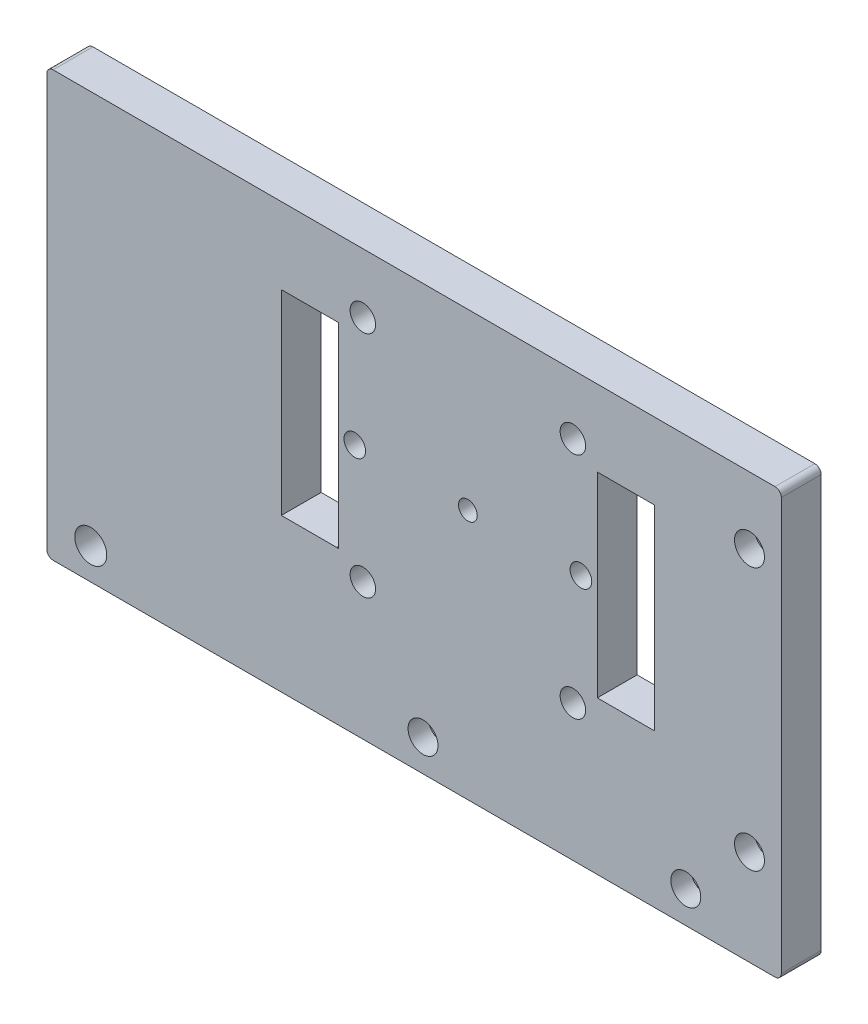
SolidWorks part; units mm, degrees
ref_plane "Front Plane" through (0, 0, 0) normal (0, 0, 1) x (1, 0, 0)
ref_plane "Top Plane" through (0, 0, 0) normal (0, 1, 0) x (1, 0, 0)
ref_plane "Right Plane" through (0, 0, 0) normal (1, 0, 0) x (0, 0, -1)
sketch "Brace Ref" plane through (0, 0, 0) normal (0, 0, 1) x (1, 0, 0)
  line B0 (-76.454, 5.6642) -> (-76.454, 10.0838)
  line B1 (-75.8588, 11.5206) -> (-73.7506, 13.6288)
  line B2 (-72.3138, 14.224) -> (-61.0148, 14.224)
  line B3 (-61.0148, 14.224) -> (-38.7641, 15.001)
  line B4 (-75.8588, 4.2274) -> (-73.7506, 2.1192)
  line B5 (-72.3138, 1.524) -> (-61.5696, 1.524)
  line B6 (-57.8366, 0) -> (-21.4114, 0)
  line B7 (-17.6784, 1.524) -> (-5.6642, 1.524)
  line B8 (-4.2274, 2.1192) -> (-2.1192, 4.2274)
  line B9 (-1.524, 5.6642) -> (-1.524, 17.6784)
  line B10 (0, 21.4114) -> (0, 57.8366)
  line B11 (-1.524, 61.5696) -> (-1.524, 72.3138)
  line B12 (-2.1192, 73.7506) -> (-4.2274, 75.8588)
  line B13 (-5.6642, 76.454) -> (-10.0838, 76.454)
  line B14 (-11.5206, 75.8588) -> (-13.6288, 73.7506)
  line B15 (-14.224, 72.3138) -> (-14.224, 61.0148)
  line B16 (-14.224, 61.0148) -> (-15.001, 38.7641)
  line B17 (-76.454, 0) -> (-76.454, 76.454) construction
  line B18 (-76.454, 0) -> (0, 0) construction
  line B19 (0, 0) -> (0, 76.454) construction
  line B20 (-76.454, 76.454) -> (0, 76.454) construction
  arc B21 (-76.454, 10.0838) -> (-75.8588, 11.5206) centre (-74.422, 10.0838) cw
  arc B22 (-73.7506, 13.6288) -> (-72.3138, 14.224) centre (-72.3138, 12.192) cw
  arc B23 (-38.7641, 15.001) -> (-27.0035, 18.4638) centre (-39.624, 39.624) ccw
  arc B24 (-27.0035, 18.4638) -> (-25.4333, 20.7849) centre (-28.6949, 21.2997) ccw
  arc B25 (-25.4333, 20.7849) -> (-20.7849, 25.4333) centre (-19.9136, 19.9136) cw
  arc B26 (-76.454, 5.6642) -> (-75.8588, 4.2274) centre (-74.422, 5.6642) ccw
  arc B27 (-73.7506, 2.1192) -> (-72.3138, 1.524) centre (-72.3138, 3.556) ccw
  arc B28 (-61.5696, 1.524) -> (-59.2587, 0.5806) centre (-61.5696, -1.778) cw
  arc B29 (-59.2587, 0.5806) -> (-57.8366, 0) centre (-57.8366, 2.032) ccw
  arc B30 (-21.4114, 0) -> (-19.9893, 0.5806) centre (-21.4114, 2.032) ccw
  arc B31 (-19.9893, 0.5806) -> (-17.6784, 1.524) centre (-17.6784, -1.778) cw
  arc B32 (-5.6642, 1.524) -> (-4.2274, 2.1192) centre (-5.6642, 3.556) ccw
  arc B33 (-2.1192, 4.2274) -> (-1.524, 5.6642) centre (-3.556, 5.6642) ccw
  arc B34 (-1.524, 17.6784) -> (-0.5806, 19.9893) centre (1.778, 17.6784) cw
  arc B35 (-0.5806, 19.9893) -> (0, 21.4114) centre (-2.032, 21.4114) ccw
  arc B36 (0, 57.8366) -> (-0.5806, 59.2587) centre (-2.032, 57.8366) ccw
  arc B37 (-0.5806, 59.2587) -> (-1.524, 61.5696) centre (1.778, 61.5696) cw
  arc B38 (-1.524, 72.3138) -> (-2.1192, 73.7506) centre (-3.556, 72.3138) ccw
  arc B39 (-4.2274, 75.8588) -> (-5.6642, 76.454) centre (-5.6642, 74.422) ccw
  arc B40 (-10.0838, 76.454) -> (-11.5206, 75.8588) centre (-10.0838, 74.422) ccw
  arc B41 (-13.6288, 73.7506) -> (-14.224, 72.3138) centre (-12.192, 72.3138) ccw
  arc B42 (-15.001, 38.7641) -> (-18.4638, 27.0035) centre (-39.624, 39.624) cw
  arc B43 (-18.4638, 27.0035) -> (-20.7849, 25.4333) centre (-21.2997, 28.6949) cw
  circle B44 centre (-70.104, 7.874) radius 4.3561
  circle B45 centre (-19.9136, 19.9136) radius 2.3813
  circle B46 centre (-7.874, 70.104) radius 4.3561
sketch_block_instance "Block1-1"
sketch_block "Block1" parameters "D1"=31.75, "D2"=30.48, "D3"=30.48, "D4"=31.75, "D5"=19.7104, "D6"=19.7104
sketch "Sketch5" plane through (0, 0, 0) normal (0, 0, 1) x (1, 0, 0)
  line L0 (-52.794, 44.294) -> (-52.794, 42.794) construction
  line L1 (-94.544, 70.544) -> (-2.794, 70.544)
  line L2 (-94.544, 70.544) -> (-94.544, 2.794)
  line L3 (-94.544, 2.794) -> (-2.794, 2.794)
  line L4 (-2.794, 70.544) -> (-2.794, 2.794)
  line L6 (-82.794, 58.794) -> (-22.794, 58.794) construction
  line L7 (-82.794, 58.794) -> (-82.794, 26.794) construction
  line L8 (-70.828, 42.794) -> (-52.794, 42.794) construction
  line L9 (-84.544, 60.544) -> (-21.044, 60.544) construction
  line L10 (-52.794, 42.794) -> (-34.76, 42.794) construction
  line L11 (-84.544, 60.544) -> (-84.544, 25.044) construction
  line L12 (-84.544, 25.044) -> (-21.044, 25.044) construction
  line L13 (-21.044, 60.544) -> (-21.044, 25.044) construction
  line L14 (-89.544, 65.544) -> (-16.044, 65.544) construction
  line L15 (-82.794, 26.794) -> (-22.794, 26.794) construction
  line L16 (-22.794, 58.794) -> (-22.794, 26.794) construction
  line L17 (-82.544, 58.394) -> (-73.694, 58.394)
  line L18 (-89.544, 65.544) -> (-89.544, 20.044) construction
  line L19 (-89.544, 20.044) -> (-16.044, 20.044) construction
  line L20 (-16.044, 65.544) -> (-16.044, 20.044) construction
  line L21 (-82.544, 58.394) -> (-82.544, 27.194)
  line L22 (-82.544, 27.194) -> (-73.694, 27.194)
  line L23 (-73.694, 58.394) -> (-73.694, 27.194)
  line L24 (-31.894, 58.394) -> (-23.044, 58.394)
  line L25 (-31.894, 58.394) -> (-31.894, 27.194)
  line L26 (-31.894, 27.194) -> (-23.044, 27.194)
  line L27 (-23.044, 58.394) -> (-23.044, 27.194)
  line L28 (-82.544, 58.394) -> (-82.794, 58.394) construction
  line L30 (-23.044, 58.394) -> (-22.794, 58.394) construction
  circle A7 centre (-52.794, 42.794) radius 1.5
  circle A10 centre (-19.9136, 19.9136) radius 3.683
  circle A14 centre (-59.944, 7.874) radius 1.5875
  circle A15 centre (-18.034, 7.874) radius 1.5875
  circle A16 centre (-7.874, 18.034) radius 1.5875
  circle A17 centre (-7.874, 59.944) radius 1.5875
  circle A18 centre (-19.9136, 19.9136) radius 2.3813 construction
  circle A19 centre (-70.828, 42.794) radius 1.6666 construction
  circle A21 centre (-34.76, 42.794) radius 1.6666 construction
  circle A22 centre (-42.794, 37.794) radius 0.5 construction
  circle A23 centre (-59.944, 7.874) radius 2.3876
  circle A24 centre (-18.034, 7.874) radius 2.3876
  circle A25 centre (-7.874, 59.944) radius 2.3876
  circle A26 centre (-7.874, 18.034) radius 2.3876
  circle A32 centre (-52.794, 42.794) radius 1.5
  circle A35 centre (-52.794, 42.794) radius 1.5
  circle A38 centre (-52.794, 42.794) radius 1.5
  point P6 (-52.794, 58.794)
  point P17 (-22.794, 42.794)
  point P25 (-52.794, 65.544)
  point P26 (-16.044, 42.794)
  point P39 (-73.694, 42.794)
  point P116 (-52.794, 42.794)
  dimension "D8" = 7.366
  dimension "D9" = 3.175
  dimension "D10" = 4.7752
  dimension "D2" = 3
  dimension "D22" = 3.3332
  dimension "D30" = 1
  dimension "D6" = 17.1196
  dimension "D7" = 17.1196
  dimension "D12" = 41.91
  dimension "D13" = 5.08
  dimension "D14" = 5.08
  dimension "D15" = 41.91
  dimension "D16" = 15.24
  dimension "D17" = 15.24
  dimension "D11" = 18.034
  dimension "D3" = 63.5
  dimension "D5" = 5
  dimension "D18" = 5
  dimension "D19" = 5
  dimension "D20" = 5
  dimension "D21" = 35.5
  dimension "D23" = 60
  dimension "D24" = 32
  dimension "D25" = 31.2
  dimension "D26" = 0.25
  dimension "D27" = 8.85
  dimension "D28" = 40
  dimension "D29" = 35
  dimension "D32" = 10
  dimension "D33" = 5
  dimension "D34" = 5
  dimension "D31" = 5
  dimension "D4" = 4
extrude "Boss-Extrude1" add sketch "Sketch5" along normal blind 6.35 contours L4 L1 L2 L3 A26 A25 A24 A23 A10 A7 L17 L23 L22 L21 L24 L27 L26 L25 | A25 A17 | A10 | A26 A16 | A24 A15 | A23 A14 region at (-48.8, 36.3508, 0) region at (-19.9136, 19.9136, 0) region at (-62.2641, 7.874, 0) region at (-20.3541, 7.874, 0) region at (-10.1941, 59.944, 0) region at (-10.1941, 18.034, 0)
hole_wizard "#8-32 Tapped Hole1" positions "3DSketch1" profile "Sketch6" tap size "#8-32" standard "ANSI Inch" end condition through all
sketch3d "3DSketch1"
  point P0 (-70.828, 42.794, 6.35)
  point P2 (-34.76, 42.794, 6.35)
sketch "Sketch6" plane through (-70.828, 42.794, 6.35) normal (1, 0, 0) x (0, -1, 0)
  line L0 (0, 0) -> (0, 6.35)
  line L1 (0, 6.35) -> (1.7272, 6.35)
  line L2 (1.7272, 6.35) -> (1.7272, 0)
  line L5 (1.7272, 0) -> (0, 0)
  line L11 (0, -6.35) -> (0, 107.95) construction
  dimension "Thru Tap Drill Dia." = 3.4544
  dimension "Thru Tap Drill Depth" = 6.35
cosmetic thread "Hole Thread1" parameters "D2"=4.1656
cosmetic thread "Hole Thread2" parameters "D2"=4.1656
extrude "Cut-Extrude2" cut sketch "Sketch5<3>" against normal blind 3.175 from surface contours A24 A15 | A26 A16 | A23 A14 | A25 A17 region at (-62.2641, 7.874, 0) region at (-20.3541, 7.874, 0) region at (-10.1941, 59.944, 0) region at (-10.1941, 18.034, 0) starting at face at (-69.1008, 42.794, 6.35)
sketch "Sketch5<3>" plane through (0, 0, 0) normal (0, 0, 1) x (1, 0, 0) same geometry as "Sketch5"
fillet "Fillet1" [suppressed] radius 6.35
sketch "Sketch8" plane through (0, 0, 0) normal (0, 0, 1) x (1, 0, 0)
  line L1 (-94.544, 2.794) -> (-119.944, 2.794)
  line L2 (-94.544, 2.794) -> (-94.544, 70.544)
  line L3 (-94.544, 70.544) -> (-119.944, 70.544)
  line L4 (-119.944, 2.794) -> (-119.944, 70.544)
  circle A0 centre (-112.944, 7.794) radius 1
  dimension "D2" = 2
  dimension "D1" = 25.4
  dimension "D3" = 5
  dimension "D4" = 7
extrude "Boss-Extrude2" add sketch "Sketch8" along normal up to surface (6.35 mm away) up to face at (-5.4864, 59.944, 6.35)
hole_wizard "1/4-20 Tapped Hole2" positions "3DSketch3" profile "Sketch10" tap size "1/4-20" standard "ANSI Inch" end condition through all
sketch3d "3DSketch3"
  line L0 (-112.944, 7.794, 6.35) -> (-112.944, 7.794, 0) construction
  point P0 (-112.944, 7.794, 6.35)
sketch "Sketch10" plane through (-112.944, 7.794, 6.35) normal (1, 0, 0) x (0, -1, 0)
  line L0 (0, 0) -> (0, 6.35)
  line L1 (0, 6.35) -> (2.5527, 6.35)
  line L2 (2.5527, 6.35) -> (2.5527, 0)
  line L5 (2.5527, 0) -> (0, 0)
  line L11 (0, -6.35) -> (0, 107.95) construction
  dimension "Thru Tap Drill Dia." = 5.1054
  dimension "Thru Tap Drill Depth" = 6.35
cosmetic thread "Hole Thread3" parameters "D2"=6.35
sketch "Sketch11" plane through (0, 0, 6.35) normal (0, 0, 1) x (1, 0, 0)
  line L1 (-69.544, 61.044) -> (-36.044, 61.044) construction
  line L2 (-69.544, 61.044) -> (-69.544, 24.544) construction
  line L3 (-69.544, 24.544) -> (-36.044, 24.544) construction
  line L4 (-36.044, 61.044) -> (-36.044, 24.544) construction
  circle A0 centre (-69.544, 61.044) radius 2.032
  circle A1 centre (-36.044, 61.044) radius 2.032
  circle A2 centre (-36.044, 24.544) radius 2.032
  circle A3 centre (-69.544, 24.544) radius 2.032
  circle A6 centre (-34.76, 42.794) radius 1.7272 construction
  circle A7 centre (-70.828, 42.794) radius 1.7272 construction
  point P4 (-34.6298, 61.297)
  point P7 (-34.419, 60.5086)
  point P12 (-34.419, 52.1365)
  point P13 (-34.419, 15.3826)
  dimension "D5" = 4.064
  dimension "D1" = 18.25
  dimension "D2" = 1.284
  dimension "D3" = 1.284
  dimension "D4" = 36.5
extrude "Cut-Extrude3" cut sketch "Sketch11" against normal through all both and the other way through all
sketch "Sketch12" plane through (0, 0, 6.35) normal (0, 0, 1) x (1, 0, 0)
  line L0 (-31.894, 27.194) -> (-23.044, 27.194) construction
  line L1 (-31.894, 58.394) -> (-32.144, 58.394)
  line L2 (-31.894, 58.394) -> (-31.894, 27.194)
  line L3 (-31.894, 27.194) -> (-32.144, 27.194)
  line L4 (-32.144, 58.394) -> (-32.144, 27.194)
  line L5 (-73.694, 58.394) -> (-73.444, 58.394)
  line L6 (-73.694, 58.394) -> (-73.694, 27.1714)
  line L7 (-73.694, 27.1714) -> (-73.444, 27.1714)
  line L8 (-73.444, 58.394) -> (-73.444, 27.1714)
  dimension "D1" = 0.25
extrude "Cut-Extrude4" cut sketch "Sketch12" against normal through all both and the other way through all
fillet "Fillet2" radius 1 4 edges at (-119.944, 70.544, 3.175) (-119.944, 2.794, 3.175) (-2.794, 70.544, 3.175) (-2.794, 2.794, 3.175)
equation "\"D18@Sketch5\"=\"D5@Sketch5\""
equation "\"D19@Sketch5\"=\"D18@Sketch5\""
equation "\"D20@Sketch5\"=\"D5@Sketch5\""
